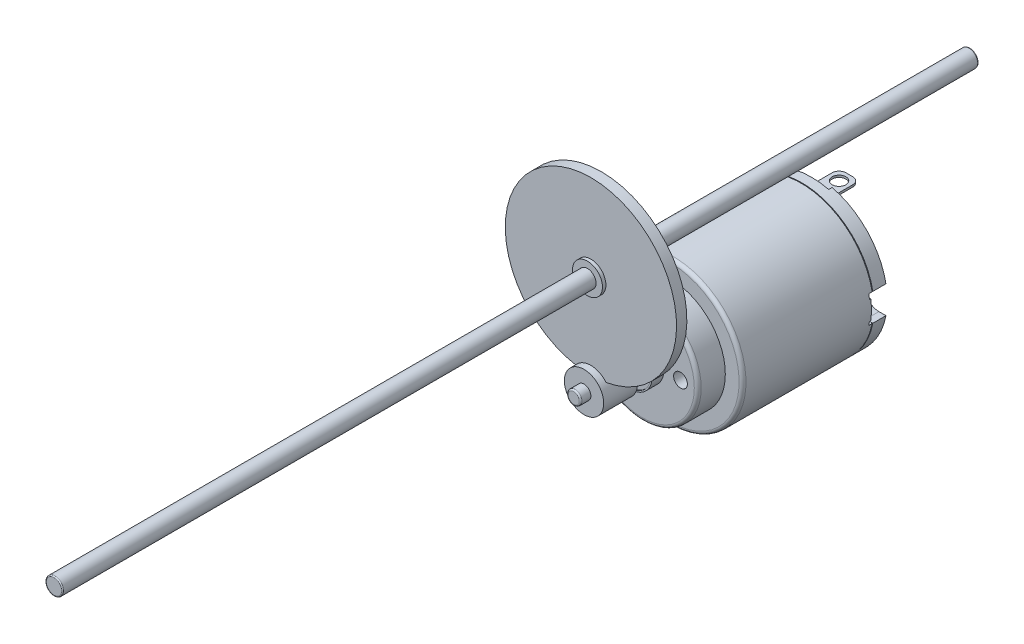
SolidWorks part; units mm, degrees
ref_plane "Plano frontal" through (0, 0, 0) normal (0, 0, 1) x (1, 0, 0)
ref_plane "Plano superior" through (0, 0, 0) normal (0, 1, 0) x (1, 0, 0)
ref_plane "Plano direito" through (0, 0, 0) normal (1, 0, 0) x (0, 0, -1)
sketch "Esboço1" plane through (0, 0, 0) normal (0, 0, 1) x (1, 0, 0)
  circle A0 centre (0, 0) radius 1
  dimension "D1" = 2
extrude "Ressalto-extrusão1" add sketch "Esboço1" along normal blind 38
ref_plane "Plano1" through (0, 0, 28) normal (0, 0, 1) x (1, 0, 0)
sketch "Esboço2" plane through (0, 0, 28) normal (0, 0, 1) x (1, 0, 0)
  circle A0 centre (0, 0) radius 8
  dimension "D1" = 16
extrude "Ressalto-extrusão2" add sketch "Esboço2" against normal blind 25
sketch "Esboço3" plane through (0, 0, 28) normal (0, 0, 1) x (1, 0, 0)
  circle A0 centre (0, 0) radius 3.075
  dimension "D1" = 6.15
extrude "Ressalto-extrusão3" add sketch "Esboço3" along normal blind 1.7
sketch "Esboço4" plane through (0, 0, 3) normal (0, 0, -1) x (-1, 0, 0)
  circle A0 centre (0, 0) radius 10.5
  dimension "D1" = 21
extrude "Ressalto-extrusão4" add sketch "Esboço4" against normal blind 21
sketch "Esboço5" plane through (0, 0, 3) normal (0, 0, -1) x (-1, 0, 0)
  circle A0 centre (0, 0) radius 3.125
  dimension "D1" = 6.25
extrude "Ressalto-extrusão5" add sketch "Esboço5" along normal blind 2
sketch "Esboço6" plane through (0, 0, 3) normal (0, 0, -1) x (-1, 0, 0)
  line L0 (0, 10.5) -> (0, -10.5) construction
  line L2 (1.5, 8.05) -> (-1.5, 8.05)
  line L3 (1.5, 8.05) -> (1.5, 7.75)
  line L4 (1.5, 7.75) -> (-1.5, 7.75)
  line L5 (-1.5, 8.05) -> (-1.5, 7.75)
  line L6 (1.5, 8.05) -> (-1.5, 7.75) construction
  line L7 (1.5, 7.75) -> (-1.5, 8.05) construction
  line L8 (1.5, -7.75) -> (-1.5, -7.75)
  line L9 (1.5, -7.75) -> (1.5, -8.05)
  line L10 (1.5, -8.05) -> (-1.5, -8.05)
  line L11 (-1.5, -7.75) -> (-1.5, -8.05)
  line L12 (1.5, -7.75) -> (-1.5, -8.05) construction
  line L13 (1.5, -8.05) -> (-1.5, -7.75) construction
  circle A0 centre (0, 0) radius 10.5 construction
  point P5 (0, 7.9)
  point P10 (0, -7.9)
  dimension "D1" = 15.5
  dimension "D2" = 0.3
  dimension "D3" = 0.3
  dimension "D4" = 3
  dimension "D5" = 3
  dimension "D6" = 7.75
extrude "Ressalto-extrusão6" add sketch "Esboço6" along normal blind 5
sketch "Esboço7" plane through (0, 8.05, 0) normal (0, 1, 0) x (1, 0, 0)
  line L0 (-1.5, 2) -> (1.5, 2) construction
  circle A0 centre (0, 0.5) radius 1
  dimension "D1" = 2
  dimension "D2" = 1.5
extrude "Corte-extrusão1" cut sketch "Esboço7" against normal blind 4
sketch "Esboço8" plane through (0, -7.75, 0) normal (0, 1, 0) x (1, 0, 0)
  circle A0 centre (0, 0.5) radius 1
extrude "Corte-extrusão2" cut sketch "Esboço8" against normal blind 4
fillet "Filete1" radius 1 4 edges at (1.5, -7.9, -2) (-1.5, -7.9, -2) (1.5, 7.9, -2) (-1.5, 7.9, -2)
fillet "Filete2" radius 0.2 2 edges at (1, 0, 0) (1, 0, 38)
sketch "Esboço9" plane through (0, 0, 3) normal (0, 0, -1) x (-1, 0, 0)
  circle A0 centre (-5.5, 0) radius 1
  circle A1 centre (5.5, 0) radius 1
  dimension "D1" = 11
  dimension "D3" = 2
  dimension "D4" = 2
  dimension "D2" = 5.5
extrude "Corte-extrusão3" cut sketch "Esboço9" against normal blind 38 and the other way blind 15
sketch "Esboço10" plane through (0, 0, 1) normal (0, 0, -1) x (-1, 0, 0)
  line L0 (2.575, 4.4181) -> (2.575, -4.909) construction
  line L2 (2.575, 4.4181) -> (2.575, -4.909)
  line L3 (2.575, -4.909) -> (3.8141, -4.909)
  line L4 (3.8141, -4.909) -> (3.8141, 4.4181)
  line L5 (3.8141, 4.4181) -> (2.575, 4.4181)
extrude "Corte-extrusão4" cut sketch "Esboço10" against normal blind 2
sketch "Esboço11" plane through (0, 0, 3) normal (0, 0, -1) x (-1, 0, 0)
  line L0 (-3.7081, 1.5) -> (-7.3485, 1.5)
  line L1 (7.3485, 1.5) -> (3.7081, 1.5)
  line L3 (7.3485, -1.5) -> (3.7081, -1.5)
  line L5 (-2.5, -7.0711) -> (-2.5, -12.5)
  line L6 (2.5, -7.0711) -> (2.5, -12.5)
  line L7 (-3.7081, -1.5) -> (-7.3485, -1.5)
  line L9 (2.5, 12.5) -> (-2.5, 12.5)
  line L10 (2.5, 12.5) -> (2.5, 7.0711)
  line L11 (2.5, -12.5) -> (-2.5, -12.5)
  line L12 (-2.5, 12.5) -> (-2.5, 7.0711)
  arc A0 (-7.3485, -1.5) -> (-2.5, -7.0711) centre (0, 0) ccw
  circle A1 centre (0, 0) radius 10.5 construction
  arc A2 (-3.7081, -1.5) -> (-2.5, -3.1225) centre (0, 0) ccw
  arc A3 (7.3485, 1.5) -> (2.5, 7.0711) centre (0, 0) ccw
  arc A4 (3.7081, 1.5) -> (2.5, 3.1225) centre (0, 0) ccw
  arc A5 (-2.5, 7.0711) -> (-7.3485, 1.5) centre (0, 0) ccw
  arc A6 (2.5, 3.1225) -> (-3.7081, 1.5) centre (0, 0) ccw
  arc A7 (2.5, -7.0711) -> (7.3485, -1.5) centre (0, 0) ccw
  arc A8 (-2.5, -3.1225) -> (3.7081, -1.5) centre (0, 0) ccw
  point P0 (0, 0)
  dimension "D2" = 3
  dimension "D3" = 8
  dimension "D1" = 5
  dimension "D4" = 25
extrude "Corte-extrusão5" cut sketch "Esboço11" against normal blind 0.5
sketch "Esboço12" plane through (0, 0, 3.5) normal (0, 0, -1) x (-1, 0, 0)
  line L0 (0, 0) -> (0, -6.6243) construction
  line L2 (0, 0) -> (13.3788, 0) construction
  arc A0 (3.375, -5.8457) -> (5.8457, -3.375) centre (0, 0) ccw
  arc A1 (2.375, -4.1136) -> (4.1136, -2.375) centre (0, 0) ccw
  arc A2 (2.375, -4.1136) -> (3.375, -5.8457) centre (2.875, -4.9796) ccw
  arc A3 (4.1136, -2.375) -> (5.8457, -3.375) centre (4.9796, -2.875) cw
  arc A8 (-3.375, 5.8457) -> (-5.8457, 3.375) centre (0, 0) ccw
  arc A9 (-4.1136, 2.375) -> (-5.8457, 3.375) centre (-4.9796, 2.875) cw
  arc A10 (-2.375, 4.1136) -> (-4.1136, 2.375) centre (0, 0) ccw
  arc A11 (-2.375, 4.1136) -> (-3.375, 5.8457) centre (-2.875, 4.9796) ccw
  dimension "D1" = 13.5
  dimension "D2" = 9.5
extrude "Corte-extrusão6" cut sketch "Esboço12" against normal blind 2
sketch "Esboço13" plane through (0, 0, 3) normal (0, 0, 1) x (1, 0, 0)
  line L1 (1.5, 8.05) -> (-1.5, 8.05)
  line L2 (1.5, 8.05) -> (1.5, 7.75)
  line L3 (1.5, 7.75) -> (-1.5, 7.75)
  line L4 (-1.5, 8.05) -> (-1.5, 7.75)
  line L5 (-1.5, -8.05) -> (1.5, -8.05)
  line L6 (-1.5, -8.05) -> (-1.5, -7.75)
  line L7 (-1.5, -7.75) -> (1.5, -7.75)
  line L8 (1.5, -8.05) -> (1.5, -7.75)
extrude "Ressalto-extrusão7" add sketch "Esboço13" along normal blind 6
ref_plane "Plano2" through (0, 0, 5) normal (0, 0, -1) x (-1, 0, 0)
sketch "Esboço14" plane through (0, 0, 5) normal (0, 0, -1) x (-1, 0, 0)
  circle A0 centre (0, 0) radius 11.3093
  circle A1 centre (0, 0) radius 10.3
  arc A2 (-2.5, 10.198) -> (-2.5, -10.198) centre (0, 0) ccw construction
  dimension "D1" = 0.2
extrude "Corte-extrusão7" cut sketch "Esboço14" along normal blind 0.1
fillet "Filete3" radius 0.5 2 edges at (8, 0, 28) (-10.5, 0, 24)
sketch "Esboço15" plane through (0, 0, 29.7) normal (0, 0, 1) x (1, 0, 0)
  circle A0 centre (0, 0) radius 2.875
  circle A1 centre (0, 0) radius 3.075 construction
  dimension "D1" = 0.2
extrude "Corte-extrusão8" cut sketch "Esboço15" against normal blind 0.1
sketch "Esboço16" plane through (0, 0, 3) normal (0, 0, -1) x (-1, 0, 0)
  line L0 (-9.2871, 2) -> (-10.3078, 2)
  line L1 (10.3078, 2) -> (9.2871, 2)
  line L3 (10.3078, -2) -> (9.2871, -2)
  line L7 (-9.2871, -2) -> (-10.3078, -2)
  arc A0 (-2.5, 10.198) -> (-2.5, -10.198) centre (0, 0) ccw construction
  arc A3 (-9.2871, -2) -> (-9.2871, 2) centre (-9.2871, 0) ccw
  arc A4 (9.2871, 2) -> (9.2871, -2) centre (9.2871, 0) ccw
  arc A5 (-10.3078, 2) -> (-10.3078, -2) centre (0, 0) ccw
  arc A6 (10.3078, -2) -> (10.3078, 2) centre (0, 0) ccw
  point P0 (0, 0)
  dimension "D1" = 4
extrude "Corte-extrusão9" cut sketch "Esboço16" against normal blind 2.5
sketch "Esboço17" plane through (0, 0, 5.5) normal (0, 0, -1) x (-1, 0, 0)
  line L0 (-8.5973, 1.3172) -> (-10.417, 1.3172)
  line L1 (10.417, 1.3172) -> (8.5973, 1.3172)
  line L2 (10.417, -1.3172) -> (10.417, -1.5)
  line L3 (10.417, -1.5) -> (8.5666, -1.5)
  line L5 (8.3688, -1.3) -> (8.3951, 1.1172)
  line L6 (10.417, -1.5) -> (10.3928, -1.4965) construction
  line L7 (-8.5973, 1.3172) -> (-8.3951, 1.1172)
  line L8 (-8.3688, -1.3) -> (-8.5666, -1.5)
  line L9 (-8.5666, -1.5) -> (-10.3923, -1.5)
  line L10 (-8.3951, 1.1172) -> (-8.3688, -1.3)
  line L11 (8.5666, -1.5) -> (8.3688, -1.3)
  line L12 (8.5973, 1.3172) -> (8.3951, 1.1172)
  arc A0 (-10.417, 1.3172) -> (-10.3923, -1.5) centre (0, 0) ccw
  arc A2 (10.3923, -1.5) -> (10.417, 1.3172) centre (0, 0) ccw
  point P0 (0, 0)
  point P6 (8.3973, 1.3172)
  point P11 (-8.3973, 1.3172)
  point P13 (-8.3666, -1.5)
  point P14 (8.3666, -1.5)
  arc M6 (-10.3078, 2) -> (-10.3078, -2) centre (0, 0) ccw
extrude "Ressalto-extrusão8" add sketch "Esboço17" along normal blind 0.2 contours L3 A2 L1 L12 L5 L11 | L10 L7 L0 L9 L8 M6 region at (9.4319, -0.0921, 5.5) region at (-9.4319, -0.0921, 5.5)
ref_plane "Plano3" through (0, 0, 36.5) normal (0, 0, 1) x (1, 0, 0)
sketch "Esboço18" plane through (0, 0, 36.5) normal (0, 0, 1) x (1, 0, 0)
  circle A0 centre (0, 0) radius 2.85
  dimension "D1" = 5.7
extrude "Ressalto-extrusão9" add sketch "Esboço18" against normal blind 4.9
ref_plane "Plano4" through (0, 0, 35.5) normal (0, 0, 1) x (1, 0, 0)
sketch "Esboço19" plane through (0, 0, 35.5) normal (0, 0, 1) x (1, 0, 0)
  line L0 (0, 0) -> (0, 14.025) construction
  line L1 (-11.4438, -2.85) -> (12.0372, -2.85) construction
  line L3 (13.7014, 26.45) -> (-10.6901, 26.45) construction
  circle A0 centre (0, 14.025) radius 12.425
  circle A2 centre (0, 0) radius 2.85 construction
  dimension "D1" = 24.85
  dimension "D2" = 29.3
extrude "Ressalto-extrusão10" add sketch "Esboço19" against normal blind 1.5
sketch "Esboço20" plane through (0, 0, 34) normal (0, 0, -1) x (-1, 0, 0)
  circle A0 centre (0, 14.025) radius 2.175
  dimension "D1" = 4.35
extrude "Ressalto-extrusão11" add sketch "Esboço20" against normal blind 2
sketch "Esboço21" plane through (0, 0, 36) normal (0, 0, 1) x (1, 0, 0)
  circle A0 centre (0, 14.025) radius 2.175
extrude "Ressalto-extrusão12" add sketch "Esboço21" against normal blind 3.9
sketch "Esboço22" plane through (0, 0, 32.1) normal (0, 0, -1) x (-1, 0, 0)
  circle A0 centre (0, 14.025) radius 1.25
  dimension "D1" = 2.5
extrude "Corte-extrusão10" cut sketch "Esboço22" against normal blind 7.9 and the other way blind 12
ref_plane "Plano5" through (0, 0, -16.5) normal (0, 0, 1) x (1, 0, 0)
sketch "Esboço23" plane through (0, 0, -16.5) normal (0, 0, 1) x (1, 0, 0)
  circle A0 centre (0, 14.025) radius 1.25
extrude "Ressalto-extrusão13" add sketch "Esboço23" along normal blind 129.9 and the other way blind 3
fillet "Filete4" radius 0.15 2 edges at (1.25, 14.025, -19.5) (1.25, 14.025, 113.4)
